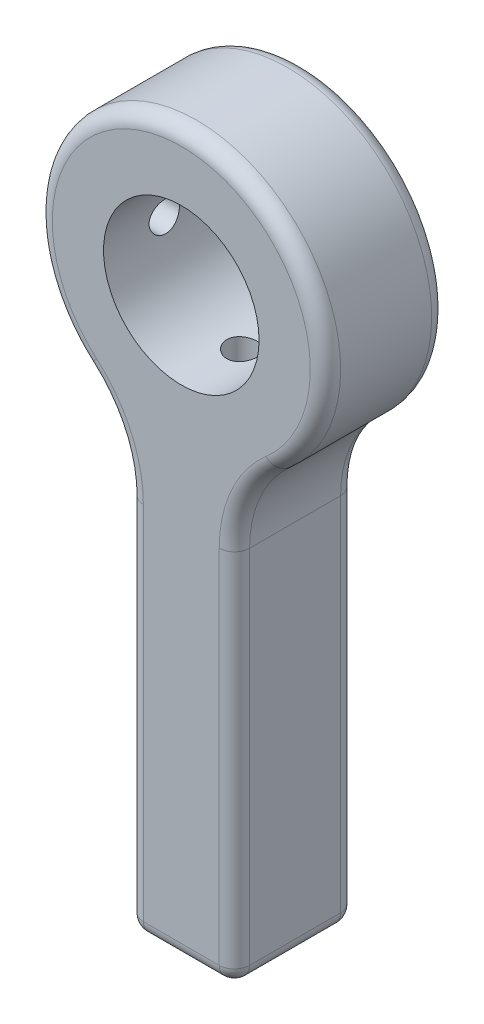
SolidWorks part; units mm, degrees
ref_plane "Front Plane" through (0, 0, 0) normal (0, 0, 1) x (1, 0, 0)
ref_plane "Top Plane" through (0, 0, 0) normal (0, 1, 0) x (1, 0, 0)
ref_plane "Right Plane" through (0, 0, 0) normal (1, 0, 0) x (0, 0, -1)
sketch "Sketch1" plane through (0, 0, 0) normal (0, 0, 1) x (1, 0, 0)
  line L0 (-4, 3) -> (-4, -3)
  line L1 (-3, -4) -> (3, -4)
  line L2 (55, 0) -> (-55, 0) construction
  line L3 (0, -55) -> (0, 55) construction
  arc A0 (-4, 3) -> (3, -4) centre (0, 0) cw
  arc A1 (-3, -4) -> (-4, -3) centre (0, 0) cw
  point P4 (-4, 0)
  point P7 (0, -4)
  dimension "D3" = 5
  dimension "D1" = 6
  dimension "D2" = 6
sketch "Sketch2" plane through (0, 0, 0) normal (0, 0, 1) x (1, 0, 0)
  line L0 (0, 0) -> (0, -38) construction
  line L1 (0, -38) -> (3.5, -38)
  line L2 (3.5, -38) -> (3.5, -8.8318)
  line L3 (0, -38) -> (-3.5, -38)
  line L4 (-3.5, -38) -> (-3.5, -8.8318)
  circle A0 centre (0, 0) radius 5.125
  arc A2 (-3.5, -8.8318) -> (3.5, -8.8318) centre (0, 0) cw
  dimension "D1" = 10.25
  dimension "D2" = 3.5
  dimension "D4" = 9.5
  dimension "D3" = 3.5
  dimension "D5" = 38
extrude "Boss-Extrude1" add sketch "Sketch2" along normal blind 8
sketch "Sketch3" plane through (0, 0, 0) normal (0, 1, 0) x (1, 0, 0)
  circle A0 centre (0, -4) radius 1
  dimension "D1" = 2
  dimension "D2" = 4
extrude "Cut-Extrude1" cut sketch "Sketch3" against normal through all
sketch "Sketch5" plane through (0, 0, 0) normal (0, 1, 0) x (1, 0, 0)
  circle A0 centre (0, -4) radius 2.375
  dimension "D1" = 4.75
extrude "Cut-Extrude2" cut sketch "Sketch5" against normal blind 88 from offset 9.5 offset against normal yes
sketch "Sketch6" plane through (0, 0, 0) normal (1, 0, 0) x (0, 0, -1)
  circle A0 centre (-4, 0) radius 1
  dimension "D1" = 4
  dimension "D2" = 2
extrude "Cut-Extrude3" cut sketch "Sketch6" against normal through all
fillet "Fillet2" radius 8 2 edges at (3.5, -8.8318, 4) (-3.5, -8.8318, 4)
fillet "Fillet1" radius 1 14 edges at (-3.5, -25.5955, 0) (0, -38, 0) (3.5, -25.5955, 0) (0, 9.5, 0) (3.5, -25.5955, 8) (0, -38, 8) (-3.5, -25.5955, 8) (0, 9.5, 8) (3.5, -38, 4) (-3.5, -38, 4) (-4.2179, -9.8786, 0) (4.2179, -9.8786, 0) (-4.2179, -9.8786, 8) (4.2179, -9.8786, 8)
